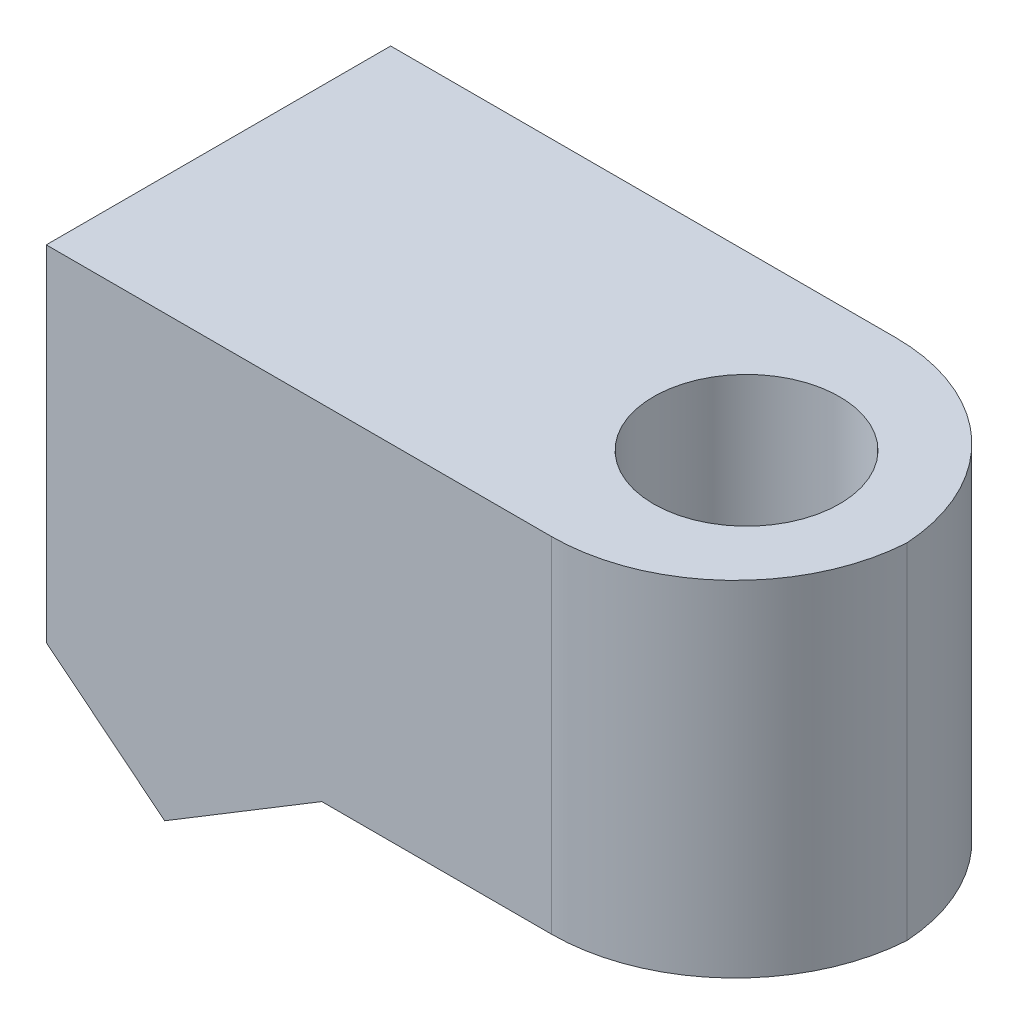
SolidWorks part; units mm, degrees
ref_plane "Спереди" through (0, 0, 0) normal (0, 0, 1) x (1, 0, 0)
ref_plane "Сверху" through (0, 0, 0) normal (0, 1, 0) x (1, 0, 0)
ref_plane "Справа" through (0, 0, 0) normal (1, 0, 0) x (0, 0, -1)
sketch "Sketch1" plane through (0, 0, 0) normal (0, 1, 0) x (1, 0, 0)
  line L0 (-15, 0) -> (15, 0) construction
  line L1 (15, -7.5) -> (-15, -7.5)
  line L2 (15, -7.5) -> (15, 7.5)
  line L3 (15, 7.5) -> (-15, 7.5)
  line L4 (-15, -7.5) -> (-15, 7.5)
  line L5 (15, -7.5) -> (-15, 7.5) construction
  line L6 (15, 7.5) -> (-15, -7.5) construction
  circle A0 centre (8, 0) radius 4.05
  point P0 (0, 0)
  dimension "D3" = 8.1
  dimension "D1" = 15
  dimension "D2" = 30
  dimension "D4" = 8
extrude "Boss-Extrude1" add sketch "Sketch1" along normal blind 15
fillet "Fillet1" radius 8 2 edges at (15, 7.5, -7.5) (15, 7.5, 7.5)
sketch "Sketch2" plane through (-15, 0, 0) normal (-1, 0, 0) x (0, 0, 1)
  line L0 (0, 15) -> (0, 0) construction
  line L1 (-7.5, 15) -> (7.5, 15) construction
  line L2 (-7.5, 0) -> (7.5, 0) construction
  line L4 (5.05, 2.45) -> (-5.05, 2.45)
  line L5 (5.05, 2.45) -> (5.05, 12.55)
  line L6 (5.05, 12.55) -> (-5.05, 12.55)
  line L7 (-5.05, 2.45) -> (-5.05, 12.55)
  line L8 (5.05, 2.45) -> (-5.05, 12.55) construction
  line L9 (5.05, 12.55) -> (-5.05, 2.45) construction
  point P6 (0, 7.5)
  dimension "D1" = 10.1
extrude "Cut-Extrude1" cut sketch "Sketch2" against normal blind 17
sketch "Sketch3" plane through (0, 0, 7.5) normal (0, 0, 1) x (1, 0, 0)
  line L0 (-3, 0) -> (-9.8422, -4.1455)
  line L1 (-9.8422, -4.1455) -> (-15, 0)
  line L3 (-3, 0) -> (-15, 0)
  line L4 (-15, 0) -> (7, 0) construction
  point P2 (0, 0)
  point P5 (0, 0)
  dimension "D1" = 110
  dimension "D2" = 8
  dimension "D4" = 10
extrude "Boss-Extrude2" add sketch "Sketch3" against normal up to surface (15 mm away) up to face at (-4, 7.5, -7.5)
sketch "Sketch4" plane through (-0.8055, 1.3296, 0) normal (0.5182, -0.8553, 0) x (0, 0, -1)
  line L0 (-7.5, -6.5658) -> (7.5, -6.5658) construction
  line L1 (-7.5, -10.5658) -> (-7.5, -2.5658) construction
  line L2 (7.5, -2.5658) -> (7.5, -10.5658) construction
  circle A0 centre (0, -6.5658) radius 3.2
  dimension "D1" = 6.4
extrude "Cut-Extrude2" cut sketch "Sketch4" against normal up to surface (3.3493 mm away) up to face at (-6.5, 2.45, 0)
